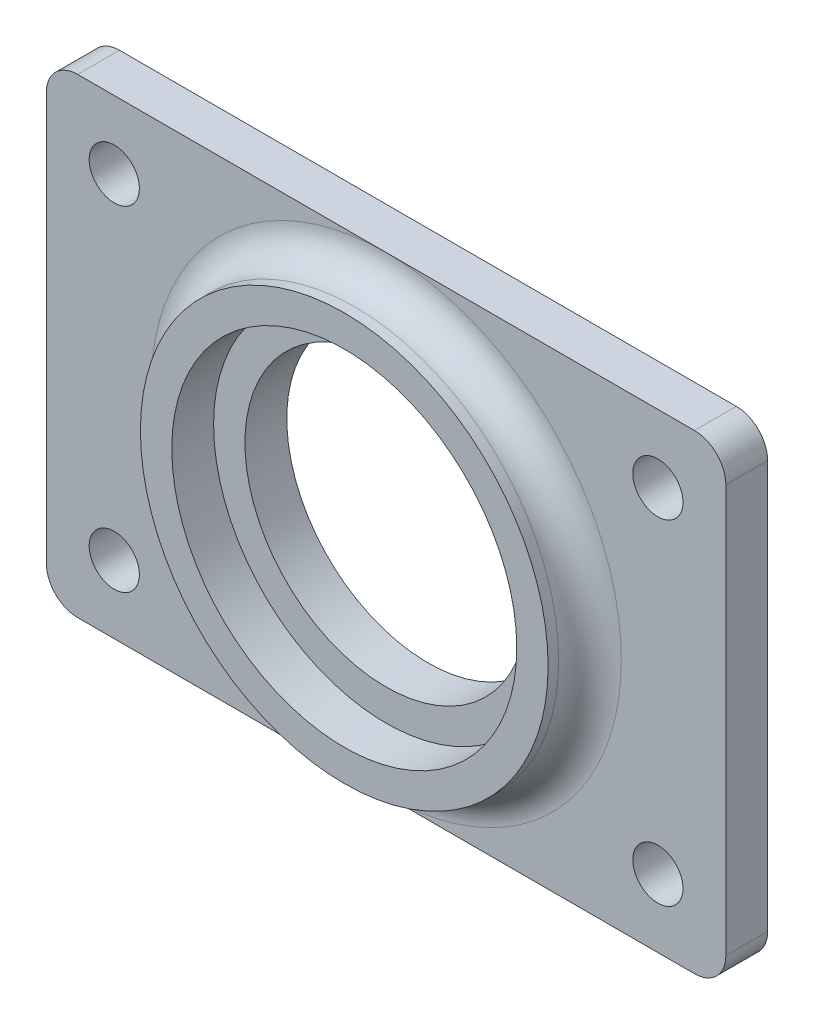
SolidWorks part; units mm, degrees
material "ABS"
ref_plane "X-Y Datum" through (0, 0, 0) normal (0, 0, 1) x (1, 0, 0)
ref_plane "X-Z Datum" through (0, 0, 0) normal (0, 1, 0) x (1, 0, 0)
ref_plane "Y-Z Datum" through (0, 0, 0) normal (1, 0, 0) x (0, 0, -1)
sketch "Sketch1" plane through (0, 0, 0) normal (0, 0, 1) x (1, 0, 0)
  line L1 (-32.5, 22.5) -> (32.5, 22.5)
  line L2 (-32.5, 22.5) -> (-32.5, -22.5)
  line L3 (-32.5, -22.5) -> (32.5, -22.5)
  line L4 (32.5, 22.5) -> (32.5, -22.5)
  line L5 (-32.5, 22.5) -> (32.5, -22.5) construction
  line L6 (-32.5, -22.5) -> (32.5, 22.5) construction
  line L7 (-26, 16) -> (26, 16) construction
  line L8 (-26, 16) -> (-26, -16) construction
  line L9 (-26, -16) -> (26, -16) construction
  line L10 (26, 16) -> (26, -16) construction
  line L11 (-26, 16) -> (26, -16) construction
  line L12 (-26, -16) -> (26, 16) construction
  circle A0 centre (0, 0) radius 16.5 construction
  circle A1 centre (-26, 16) radius 2
  circle A2 centre (-26, -16) radius 2
  circle A3 centre (26, -16) radius 2
  circle A4 centre (26, 16) radius 2
  dimension "D1" = 33
  dimension "D4" = 4
  dimension "D2" = 65
  dimension "D3" = 45
  dimension "D5" = 32
  dimension "D6" = 52
extrude "Boss-Extrude1" add sketch "Sketch1" along normal blind 4 contours L4 L1 L2 L3 A4 A3 A2 A1 | A1 | A2 | A3 | A4 region at (0, 0, 0) region at (-26, 16, 0) region at (-26, -16, 0) region at (26, -16, 0) region at (26, 16, 0)
sketch "Sketch4" plane through (0, 0, 4) normal (0, 0, 1) x (1, 0, 0)
  circle A0 centre (0, 0) radius 16.5
  circle A1 centre (0, 0) radius 19.5
  dimension "D1" = 33
  dimension "D2" = 3
extrude "Boss-Extrude3" add sketch "Sketch4" along normal blind 4
sketch "Sketch5" plane through (0, 0, 4) normal (0, 0, 1) x (1, 0, 0)
  circle A0 centre (0, 0) radius 13.5
  dimension "D1" = 27
extrude "Cut-Extrude2" cut sketch "Sketch5" against normal through all
hole_wizard "M4 Clearance Hole1" positions "Sketch8" profile "Sketch7" hole size "M4" standard "ANSI Metric" end condition through all
sketch "Sketch8" plane through (0, 0, 4) normal (0, 0, 1) x (1, 0, 0)
  point P0 (26, 16)
  point P3 (26, -16)
  point P6 (-26, -16)
  point P9 (-26, 16)
sketch "Sketch7" plane through (26, 16, 4) normal (1, 0, 0) x (0, -1, 0)
  line L0 (0, 0) -> (0, 4)
  line L1 (0, 4) -> (2.4, 4)
  line L2 (2.4, 4) -> (2.4, 0)
  line L5 (2.4, 0) -> (0, 0)
  line L11 (0, -6.35) -> (0, 107.95) construction
  dimension "Thru Hole Dia." = 4.8
  dimension "Thru Hole Depth" = 4
fillet "Fillet1" radius 3 5 edges at (-32.5, -22.5, 2) (-32.5, 22.5, 2) (19.5, 0, 4) (32.5, -22.5, 2) (32.5, 22.5, 2)
